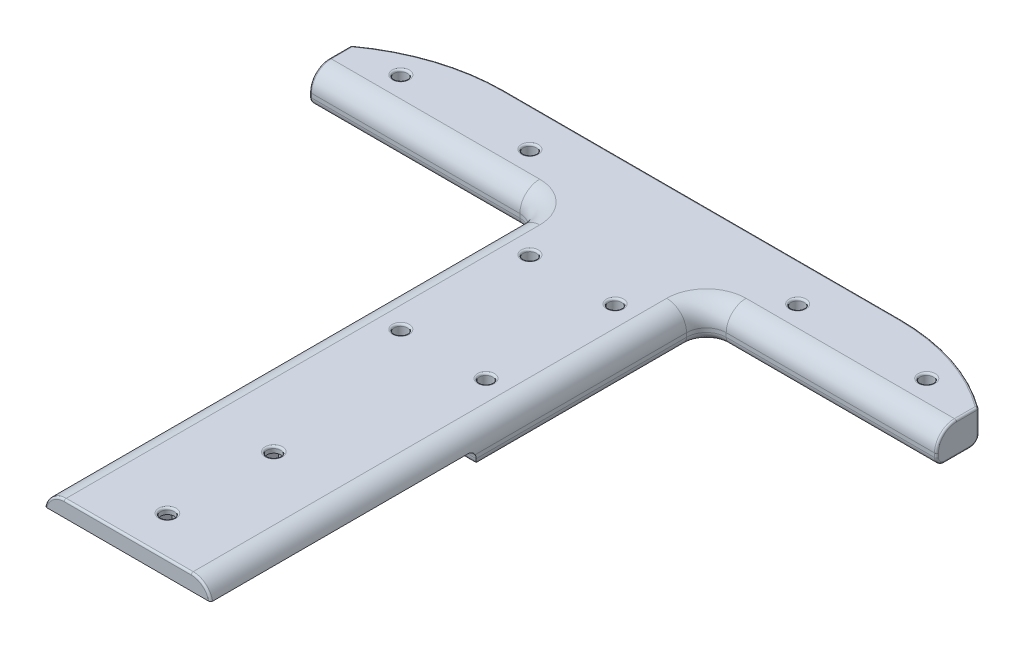
SolidWorks part; units mm, degrees
ref_plane "Front Plane" through (0, 0, 0) normal (0, 0, 1) x (1, 0, 0)
ref_plane "Top Plane" through (0, 0, 0) normal (0, 1, 0) x (1, 0, 0)
ref_plane "Right Plane" through (0, 0, 0) normal (1, 0, 0) x (0, 0, -1)
sketch "Sketch1" plane through (0, 0, 0) normal (0, 1, 0) x (1, 0, 0)
  line L1 (-79, 29) -> (-21, 29) construction
  line L2 (-79, 29) -> (-79, -29) construction
  line L3 (-79, -29) -> (-21, -29) construction
  line L4 (-21, 29) -> (-21, -29) construction
  line L5 (-79, 29) -> (-21, -29) construction
  line L6 (-79, -29) -> (-21, 29) construction
  circle A2 centre (-50, 0) radius 42.5 construction
  circle A3 centre (50, 0) radius 42.5 construction
  circle A4 centre (50, 0) radius 49 construction
  circle A5 centre (-50, 0) radius 49 construction
  circle A6 centre (-50, 0) radius 29 construction
  dimension "D1" = 85
  dimension "D2" = 58
  dimension "D3" = 29
  dimension "D4" = 98
  dimension "D5" = 50
  dimension "D6" = 50
sketch "Sketch2" plane through (0, 0, 0) normal (0, 1, 0) x (1, 0, 0)
  line L5 (-79, 29) -> (-79, 39.4968)
  line L6 (-21, -29) -> (-21, 29)
  line L7 (-21, 29) -> (-79, 29)
  line L9 (0, -53.9) -> (0, 53.9) construction
  line L13 (-50, 49) -> (50, 49)
  line L14 (-21, -29) -> (21, -29)
  line L15 (21, 29) -> (79, 29)
  line L16 (21, -29) -> (21, 29)
  line L17 (79, 29) -> (79, 39.4968)
  arc A0 (-79, 39.4968) -> (-50, 49) centre (-50, 0) cw
  arc A1 (79, 39.4968) -> (50, 49) centre (50, 0) ccw
  point P3 (0, 49)
  point P13 (0, 49)
  point P16 (0, -29)
  point P21 (0, -29)
  dimension "D1" = 49
extrude "Boss-Extrude1" add sketch "Sketch2" against normal blind 8
sketch "Sketch6" plane through (0, 0, 0) normal (0, 1, 0) x (1, 0, 0)
  line L0 (0, 0) -> (-50, 0) construction
  line L1 (0, 0) -> (50, 0) construction
  line L5 (0, -53.9) -> (0, 53.9) construction
  circle A0 centre (-10.7351, -16.264) radius 1.65
  circle A2 centre (-50, 0) radius 42.5 construction
  circle A3 centre (-65.0626, -38.3499) radius 1.65 [skipped]
  circle A4 centre (-87.4338, -15.8606) radius 1.65 [skipped]
  circle A5 centre (-87.4338, 15.8606) radius 1.65 [skipped]
  circle A6 centre (-65.0626, 38.3499) radius 1.65 [skipped]
  circle A8 centre (-10.7351, 16.264) radius 1.65
  circle A10 centre (10.7351, 16.264) radius 1.65
  circle A11 centre (10.7351, -16.264) radius 1.65
  circle A13 centre (-33.3417, -38.5167) radius 1.65 [skipped]
  circle A14 centre (-33.3417, 38.5167) radius 1.65 [skipped]
  circle A15 centre (-33.736, 39.2649) radius 1.65
  circle A16 centre (-66.264, 39.2649) radius 1.65
  circle A17 centre (66.264, 39.2649) radius 1.65
  circle A18 centre (33.736, 39.2649) radius 1.65
  dimension "D1" = 3.3
  dimension "D2" = 22.5
  dimension "D4" = 42.5
  dimension "D5" = 22.5
  dimension "D6" = 45
  dimension "D7" = 45
  dimension "D3" = 8
extrude "Cut-Extrude1" cut sketch "Sketch6" against normal up to surface (8 mm away) up to face at (0, -8, -23.9624)
sketch "Sketch9" plane through (0, 0, 29) normal (0, 0, 1) x (1, 0, 0)
  line L1 (-1, 0) -> (-99, 0) construction
  line L2 (-21, 0) -> (-21, -4)
  line L3 (-21, -4) -> (21, -4)
  line L5 (21, -4) -> (21, 0)
  line L6 (99, 0) -> (1, 0) construction
  line L7 (21, 0) -> (-21, 0)
  line L8 (-21, -8) -> (-21, 0) construction
  line L9 (21, -8) -> (21, 0) construction
  dimension "D1" = 4
extrude "Boss-Extrude2" add sketch "Sketch9" along normal blind 66.8
sketch "Sketch13" plane through (0, -4, 0) normal (0, -1, 0) x (1, 0, 0)
  line L0 (-21, 95.8) -> (21, 95.8) construction
  line L1 (50, 49) -> (-50, 49) construction
  circle A0 centre (0, 59) radius 1.7
  circle A1 centre (0, 85.8) radius 1.7
  circle A2 centre (50, 0) radius 49 construction
  circle A3 centre (-50, 0) radius 49 construction
  dimension "D1" = 3.4
  dimension "D2" = 10
  dimension "D3" = 10
extrude "Cut-Extrude2" cut sketch "Sketch13" against normal up to surface (4 mm away) up to face at (-33.736, 0, -37.6149)
sketch "Sketch14" plane through (0, -4, 0) normal (0, -1, 0) x (1, 0, 0)
  line L1 (-3.2332, 59) -> (-1.6166, 56.2)
  line L2 (-1.6166, 56.2) -> (1.6166, 56.2)
  line L3 (1.6166, 56.2) -> (3.2332, 59)
  line L4 (3.2332, 59) -> (1.6166, 61.8)
  line L5 (1.6166, 61.8) -> (-1.6166, 61.8)
  line L6 (-1.6166, 61.8) -> (-3.2332, 59)
  line L7 (-3.2332, 85.8) -> (-1.6166, 83)
  line L8 (-1.6166, 83) -> (1.6166, 83)
  line L9 (1.6166, 83) -> (3.2332, 85.8)
  line L10 (3.2332, 85.8) -> (1.6166, 88.6)
  line L11 (1.6166, 88.6) -> (-1.6166, 88.6)
  line L12 (-1.6166, 88.6) -> (-3.2332, 85.8)
  circle A0 centre (0, 59) radius 2.8 construction
  circle A1 centre (0, 85.8) radius 2.8 construction
  dimension "D1" = 5.6
extrude "Cut-Extrude3" cut sketch "Sketch14" against normal blind 2.5
fillet "Fillet1" radius 5 2 edges at (-21, -4, -29) (21, -4, -29)
fillet "Fillet9" radius 2 11 edges at (-21, -8, 2.5) (-52.5, -8, -29) (21, -8, 2.5) (22.4645, -8, -27.5355) (65.2587, -8, -46.5636) (-65.2587, -8, -46.5636) (-22.4645, -8, -27.5355) (52.5, -8, -29) (0, -4, 29) (0, -8, -49) (0, -8, 29)
fillet "Fillet10" radius 5 6 edges at (21, 0, 35.9) (22.4645, 0, -27.5355) (-21, 0, 35.9) (-22.4645, 0, -27.5355) (52.5, 0, -29) (-52.5, 0, -29)
fillet "Fillet11" radius 0.5 38 edges at (-79, -3, -39.4968) (-79, -7.4904, -38.6672) (-79, -7.4142, -29.5858) (-79, -5.5, -29) (-79, -1.4645, -30.4645) (79, -3, -39.4968) (79, -7.439, -38.7362) (79, -7.4142, -29.5858) (79, -5.5, -29) (79, -1.4645, -30.4645) (19.1623, -1.127, 95.8) (-19.1623, -1.127, 95.8) (79, -8, -33.9932) (-79, -8, -33.9932) (-10.7351, -8, 17.914) (10.7351, -8, 17.914) (10.7351, -8, -14.614) (33.736, -8, -37.6149) (66.264, -8, -37.6149) (-10.7351, -8, -14.614) (-66.264, -8, -37.6149) (-33.736, -8, -37.6149) (-79, 0, -36.7484) (-65.2587, 0, -46.5636) (0, 0, -49) (65.2587, 0, -46.5636) (79, 0, -36.7484) (0, 0, 95.8) (-10.7351, 0, 17.914) (10.7351, 0, 14.614) (10.7351, 0, -17.914) (33.736, 0, -40.9149) (66.264, 0, -40.9149) (-10.7351, 0, -14.614) (-66.264, 0, -37.6149) (-33.736, 0, -37.6149) (0, 0, 87.5) (0, 0, 60.7)
